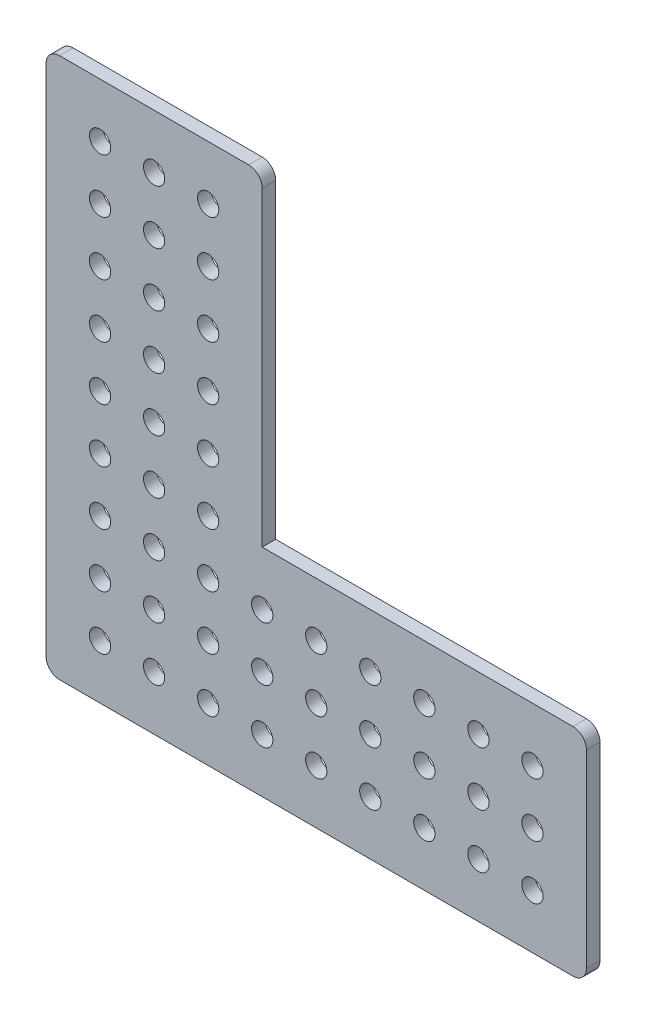
SolidWorks part; units mm, degrees
ref_plane "Front Plane" through (0, 0, 0) normal (0, 0, 1) x (1, 0, 0)
ref_plane "Top Plane" through (0, 0, 0) normal (0, 1, 0) x (1, 0, 0)
ref_plane "Right Plane" through (0, 0, 0) normal (1, 0, 0) x (0, 0, -1)
sketch "Sketch1" plane through (0, 0, 0) normal (0, 0, 1) x (1, 0, 0)
  line L1 (-24.465, 14.6479) -> (99.36, 14.6479)
  line L2 (-24.465, 14.6479) -> (-24.465, -32.9771)
  line L3 (-21.29, -36.1521) -> (99.36, -36.1521)
  line L4 (102.535, 11.4729) -> (102.535, -32.9771)
  line L5 (-21.29, 90.8479) -> (23.16, 90.8479)
  line L6 (-24.465, 87.6729) -> (-24.465, 14.6479)
  line L7 (-24.465, 14.6479) -> (26.335, 14.6479)
  line L8 (26.335, 87.6729) -> (26.335, 14.6479)
  arc A0 (-24.465, -32.9771) -> (-21.29, -36.1521) centre (-21.29, -32.9771) ccw
  arc A1 (99.36, -36.1521) -> (102.535, -32.9771) centre (99.36, -32.9771) ccw
  arc A2 (99.36, 14.6479) -> (102.535, 11.4729) centre (99.36, 11.4729) cw
  arc A3 (23.16, 90.8479) -> (26.335, 87.6729) centre (23.16, 87.6729) cw
  arc A4 (-21.29, 90.8479) -> (-24.465, 87.6729) centre (-21.29, 87.6729) ccw
  point P10 (-24.465, -36.1521)
  point P13 (102.535, -36.1521)
  point P16 (102.535, 14.6479)
  point P19 (26.335, 90.8479)
  point P22 (-24.465, 90.8479)
  dimension "D5" = 3.175
  dimension "D1" = 50.8
  dimension "D2" = 50.8
  dimension "D3" = 127
  dimension "D4" = 76.2
extrude "Boss-Extrude1" add sketch "Sketch1" along normal blind 3.175 contours L8 L5 L6 L1 | L4 L1 L2 L3 region at (0.935, 52.706, 0) region at (39.0139, -10.7439, 0)
sketch "Sketch2" plane through (0, 0, 3.175) normal (0, 0, 1) x (1, 0, 0)
  line L0 (-24.465, 87.6729) -> (-24.465, -32.9771) construction
  line L1 (-21.29, 90.8479) -> (23.16, 90.8479) construction
  line L2 (102.535, 11.4729) -> (102.535, -32.9771) construction
  line L3 (-21.29, -36.1521) -> (99.36, -36.1521) construction
  circle A0 centre (-11.765, 78.1479) radius 2.5
  circle A1 centre (89.835, -23.4521) radius 2.5
  circle A2 centre (0.935, 78.1479) radius 2.5
  circle A3 centre (13.635, 78.1479) radius 2.5
  circle A4 centre (0.935, 65.4479) radius 2.5
  circle A5 centre (13.635, 65.4479) radius 2.5
  circle A6 centre (0.935, 52.7479) radius 2.5
  circle A7 centre (13.635, 52.7479) radius 2.5
  circle A8 centre (0.935, 40.0479) radius 2.5
  circle A9 centre (13.635, 40.0479) radius 2.5
  circle A10 centre (0.935, 27.3479) radius 2.5
  circle A11 centre (13.635, 27.3479) radius 2.5
  circle A12 centre (0.935, 14.6479) radius 2.5
  circle A13 centre (13.635, 14.6479) radius 2.5
  circle A14 centre (0.935, 1.9479) radius 2.5
  circle A15 centre (13.635, 1.9479) radius 2.5
  circle A16 centre (0.935, -10.7521) radius 2.5
  circle A17 centre (13.635, -10.7521) radius 2.5
  circle A18 centre (0.935, -23.4521) radius 2.5
  circle A19 centre (13.635, -23.4521) radius 2.5
  circle A20 centre (-11.765, 65.4479) radius 2.5
  circle A21 centre (-11.765, 52.7479) radius 2.5
  circle A22 centre (-11.765, 40.0479) radius 2.5
  circle A23 centre (-11.765, 27.3479) radius 2.5
  circle A24 centre (-11.765, 14.6479) radius 2.5
  circle A25 centre (-11.765, 1.9479) radius 2.5
  circle A26 centre (-11.765, -10.7521) radius 2.5
  circle A27 centre (-11.765, -23.4521) radius 2.5
  circle A28 centre (77.135, -23.4521) radius 2.5
  circle A29 centre (64.435, -23.4521) radius 2.5
  circle A30 centre (51.735, -23.4521) radius 2.5
  circle A31 centre (39.035, -23.4521) radius 2.5
  circle A32 centre (26.335, -23.4521) radius 2.5
  circle A33 centre (77.135, -10.7521) radius 2.5
  circle A34 centre (64.435, -10.7521) radius 2.5
  circle A35 centre (51.735, -10.7521) radius 2.5
  circle A36 centre (39.035, -10.7521) radius 2.5
  circle A37 centre (26.335, -10.7521) radius 2.5
  circle A38 centre (77.135, 1.9479) radius 2.5
  circle A39 centre (64.435, 1.9479) radius 2.5
  circle A40 centre (51.735, 1.9479) radius 2.5
  circle A41 centre (39.035, 1.9479) radius 2.5
  circle A42 centre (26.335, 1.9479) radius 2.5
  circle A43 centre (89.835, -10.7521) radius 2.5
  circle A44 centre (89.835, 1.9479) radius 2.5
  dimension "D1" = 5
  dimension "D4" = 5
  dimension "D2" = 12.7
  dimension "D3" = 12.7
  dimension "D5" = 12.7
  dimension "D6" = 12.7
  dimension "D7" = 3
  dimension "D8" = 6
extrude "Cut-Extrude1" cut sketch "Sketch2" against normal through all
